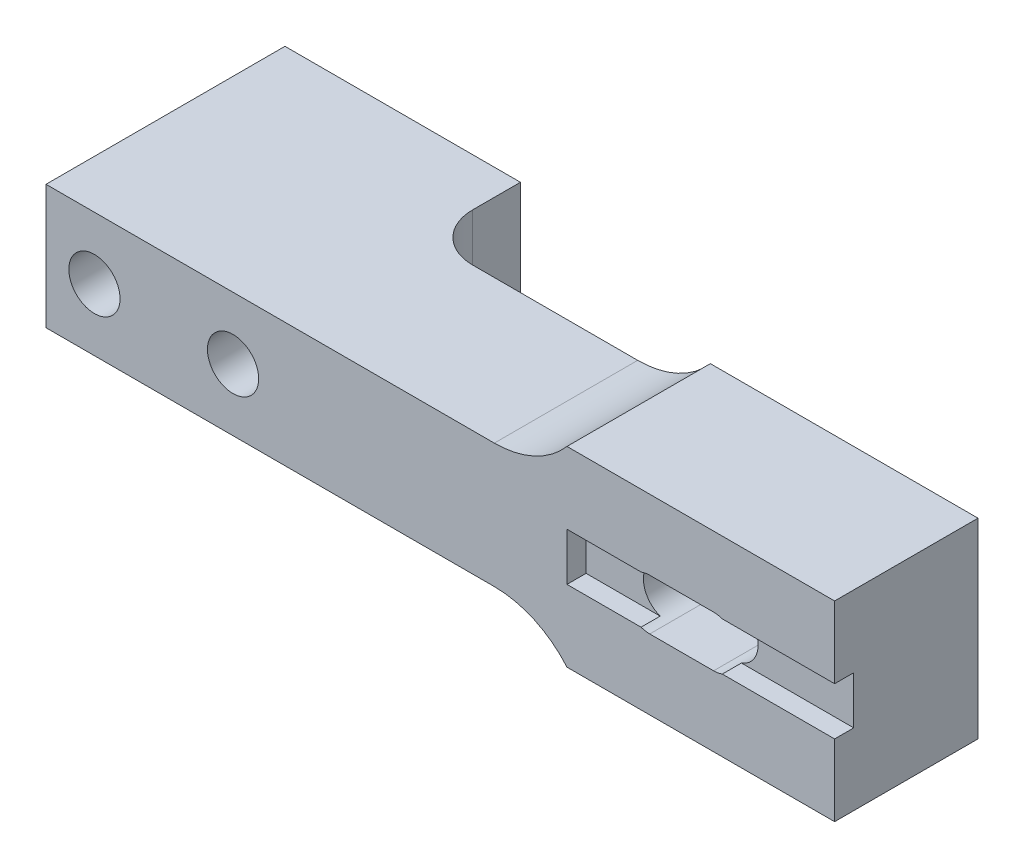
SolidWorks part; units mm, degrees
ref_plane "Front Plane" through (0, 0, 0) normal (0, 0, 1) x (1, 0, 0)
ref_plane "Top Plane" through (0, 0, 0) normal (0, 1, 0) x (1, 0, 0)
ref_plane "Right Plane" through (0, 0, 0) normal (1, 0, 0) x (0, 0, -1)
sketch "Sketch1" plane through (0, 0, 0) normal (0, 0, 1) x (1, 0, 0)
  line L0 (0, 0) -> (80, 0) construction
  line L1 (0, 13) -> (24.634, 13)
  line L2 (0, 13) -> (0, 0)
  line L3 (0, 0) -> (24.634, 0)
  line L4 (24.634, 13) -> (24.634, 0)
  line L5 (5.067, 6.5) -> (0, 6.5) construction
  line L6 (24.634, 6.5) -> (19.567, 6.5) construction
extrude "Boss-Extrude1" add sketch "Sketch1" along normal blind 10
sketch "Sketch4" plane through (0, 0, 10) normal (0, 0, 1) x (1, 0, 0)
  line L0 (24.634, 13) -> (0, 13) construction
  line L1 (0, 0) -> (82.5, 0)
  line L2 (0, 0) -> (0, 13)
  line L3 (0, 13) -> (82.5, 13)
  line L4 (82.5, 0) -> (82.5, 13)
  line L5 (80, 0) -> (80, 13) construction
  dimension "D1" = 2.5
extrude "Boss-Extrude4" add sketch "Sketch4" along normal blind 15
sketch "Sketch5" plane through (0, 0, 25) normal (0, 0, 1) x (1, 0, 0)
  line L0 (82.5, 0) -> (82.5, 13) construction
  line L1 (54.5, -3.5) -> (82.5, -3.5)
  line L2 (54.5, -3.5) -> (54.5, 0)
  line L3 (54.5, 16.5) -> (82.5, 16.5)
  line L4 (82.5, -3.5) -> (82.5, 0)
  line L5 (54.5, -3.5) -> (82.5, 16.5) construction
  line L6 (68.5, 0) -> (68.5, 13) construction
  line L7 (0, 0) -> (82.5, 0) construction
  line L8 (82.5, 13) -> (0, 13) construction
  line L9 (54.5, 0) -> (82.5, 0)
  line L10 (82.5, 13) -> (54.5, 13)
  line L11 (54.5, 13) -> (54.5, 16.5)
  line L12 (82.5, 13) -> (82.5, 16.5)
  point P13 (68.5, 6.5)
  point P14 (68.5, 6.5)
  dimension "D1" = 20
  dimension "D2" = 28
extrude "Boss-Extrude5" add sketch "Sketch5" against normal up to surface (15 mm away) up to face at (53.567, 6.5, 10)
sketch "Sketch6" plane through (0, 0, 25) normal (0, 0, 1) x (1, 0, 0)
  line L0 (54.5, 0) -> (54.5, 13) construction
  line L1 (63.16, 6.5) -> (69.84, 6.5) construction
  line L2 (63.16, 9.16) -> (69.84, 9.16)
  line L3 (63.16, 3.84) -> (69.84, 3.84)
  arc A0 (63.16, 9.16) -> (63.16, 3.84) centre (63.16, 6.5) ccw
  arc A1 (69.84, 3.84) -> (69.84, 9.16) centre (69.84, 6.5) ccw
  point P6 (66.5, 6.5)
  point P11 (61.2926, 6.3747)
  point P12 (63.089, 6.7529)
  point P13 (63.2695, 6.5)
  point P14 (69.1872, 6.5882)
  point P15 (54.5, 6.5)
  point P16 (60.5, 6.5)
  point P17 (72.5, 6.5)
  dimension "D1" = 5.32
  dimension "D2" = 6
  dimension "D3" = 12
extrude "Cut-Extrude1" cut sketch "Sketch6" against normal through all
sketch "Sketch7" plane through (0, 0, 25) normal (0, 0, 1) x (1, 0, 0)
  line L0 (54.5, 13) -> (54.5, 0) construction
  line L1 (54.5, 6.5) -> (82.5, 6.5) construction
  line L2 (82.5, -3.5) -> (82.5, 16.5) construction
  line L3 (68.5, 6.5) -> (68.5, 9) construction
  line L4 (54.5, 9) -> (82.5, 9)
  line L5 (54.5, 9) -> (54.5, 4)
  line L6 (54.5, 4) -> (82.5, 4)
  line L7 (82.5, 9) -> (82.5, 4)
  line L8 (68.5, 6.5) -> (68.5, 4) construction
  point P14 (68.5, 9.6773)
  dimension "D1" = 5
extrude "Cut-Extrude2" cut sketch "Sketch7" against normal blind 2
sketch "Sketch11" plane through (0, 0, 0) normal (0, 0, -1) x (-1, 0, 0)
  line L0 (0, 6.5) -> (-24.634, 6.5) construction
  line L1 (0, 13) -> (0, 0) construction
  line L2 (-24.634, 0) -> (-24.634, 13) construction
  circle A0 centre (-5.067, 6.5) radius 2.68
  circle A1 centre (-19.567, 6.5) radius 2.68
  dimension "D3" = 5.36
  dimension "D4" = 5.36
  dimension "D1" = 5.067
  dimension "D2" = 14.5
extrude "Cut-Extrude3" cut sketch "Sketch11" against normal through all
fillet "Fillet1" radius 10 2 edges at (54.5, 13, 17.5) (54.5, 0, 17.5)
fillet "Fillet2" radius 5 1 edges at (24.634, 6.5, 10)
